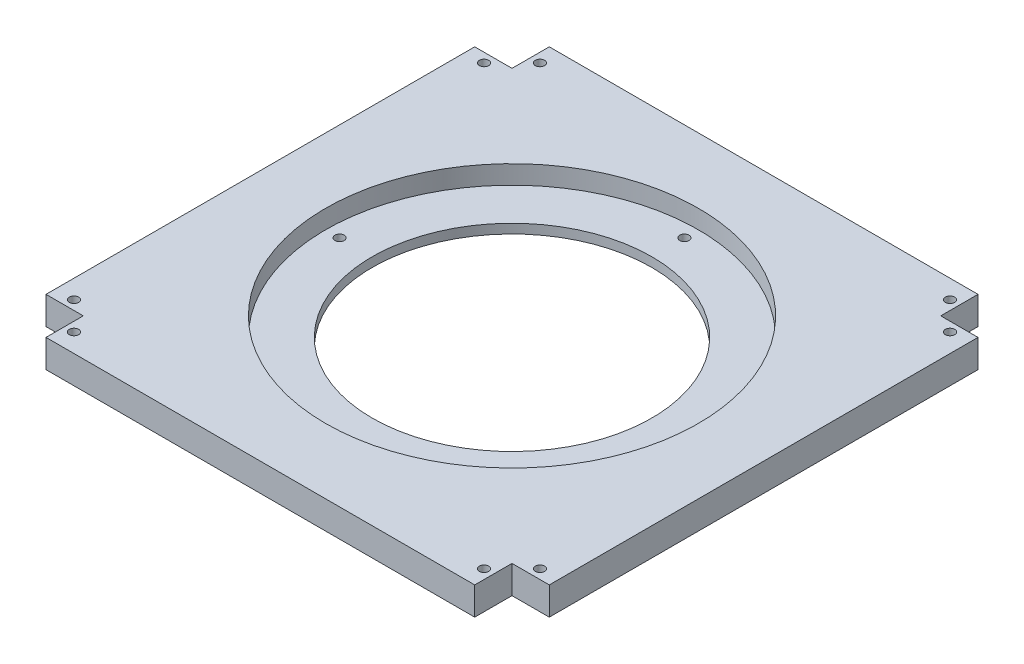
SolidWorks part; units mm, degrees
ref_plane "Front Plane" through (0, 0, 0) normal (0, 0, 1) x (1, 0, 0)
ref_plane "Top Plane" through (0, 0, 0) normal (0, 1, 0) x (1, 0, 0)
ref_plane "Right Plane" through (0, 0, 0) normal (1, 0, 0) x (0, 0, -1)
sketch "Sketch1" plane through (0, 0, 0) normal (0, 1, 0) x (1, 0, 0)
  line L21 (0, 0) -> (270, 0)
  line L22 (0, 0) -> (0, 270)
  line L23 (0, 270) -> (270, 270)
  line L24 (270, 0) -> (270, 270)
  line L44 (135, 270) -> (135, 0) construction
  line L45 (0, 135) -> (270, 135) construction
  dimension "D1" = 270
  dimension "D2" = 270
extrude "Boss-Extrude1" add sketch "Sketch1" along normal blind 15
sketch "Sketch8" plane through (0, 15, 0) normal (0, 1, 0) x (1, 0, 0)
  line L1 (0, 270) -> (20, 270)
  line L2 (0, 270) -> (0, 250)
  line L3 (0, 250) -> (20, 250)
  line L4 (20, 270) -> (20, 250)
  line L5 (270, 270) -> (250, 270)
  line L6 (270, 270) -> (270, 250)
  line L7 (270, 250) -> (250, 250)
  line L8 (250, 270) -> (250, 250)
  line L9 (270, 0) -> (250, 0)
  line L10 (270, 0) -> (270, 20)
  line L11 (270, 20) -> (250, 20)
  line L12 (250, 0) -> (250, 20)
  line L13 (0, 0) -> (20, 0)
  line L14 (0, 0) -> (0, 20)
  line L15 (0, 20) -> (20, 20)
  line L16 (20, 0) -> (20, 20)
  dimension "D1" = 20
  dimension "D2" = 20
  dimension "D3" = 20
  dimension "D4" = 20
  dimension "D5" = 20
  dimension "D6" = 20
  dimension "D7" = 20
  dimension "D8" = 20
extrude "Cut-Extrude1" cut sketch "Sketch8" against normal through all
sketch "Sketch9" plane through (0, 15, 0) normal (0, 1, 0) x (1, 0, 0)
  line L0 (135, 270) -> (135, 0) construction
  line L1 (250, 270) -> (20, 270) construction
  line L2 (20, 0) -> (250, 0) construction
  line L3 (0, 135) -> (270, 135) construction
  line L4 (0, 250) -> (0, 20) construction
  line L5 (270, 20) -> (270, 250) construction
  line L6 (260, 250) -> (260, 20) construction
  line L7 (250, 250) -> (270, 250) construction
  line L8 (270, 20) -> (250, 20) construction
  line L9 (250, 10) -> (20, 10) construction
  line L10 (250, 20) -> (250, 0) construction
  line L11 (20, 0) -> (20, 20) construction
  line L12 (10, 250) -> (10, 20) construction
  line L13 (0, 250) -> (20, 250) construction
  line L14 (20, 20) -> (0, 20) construction
  line L15 (20, 260) -> (250, 260) construction
  line L16 (20, 250) -> (20, 270) construction
  line L17 (250, 270) -> (250, 250) construction
  circle A0 centre (10, 245) radius 2.5
  circle A1 centre (10, 25) radius 2.5
  circle A2 centre (25, 10) radius 2.5
  circle A3 centre (245, 10) radius 2.5
  circle A4 centre (260, 25) radius 2.5
  circle A5 centre (260, 245) radius 2.5
  circle A6 centre (245, 260) radius 2.5
  circle A7 centre (25, 260) radius 2.5
  dimension "D1" = 5
  dimension "D2" = 5
  dimension "D3" = 5
  dimension "D4" = 5
  dimension "D5" = 5
  dimension "D6" = 5
  dimension "D7" = 5
  dimension "D8" = 5
  dimension "D9" = 5
  dimension "D10" = 5
  dimension "D11" = 5
  dimension "D12" = 5
  dimension "D13" = 5
  dimension "D14" = 5
  dimension "D15" = 5
  dimension "D16" = 5
extrude "Cut-Extrude2" cut sketch "Sketch9" against normal through all
sketch "Sketch10" plane through (0, 15, 0) normal (0, 1, 0) x (1, 0, 0)
  line L0 (135, 270) -> (135, 0) construction
  line L2 (250, 270) -> (20, 270) construction
  line L3 (20, 0) -> (250, 0) construction
  line L4 (0, 135) -> (270, 135) construction
  line L5 (0, 250) -> (0, 20) construction
  line L6 (270, 20) -> (270, 250) construction
  circle A0 centre (135, 135) radius 100
  dimension "D1" = 200
extrude "Cut-Extrude3" cut sketch "Sketch10" against normal blind 10
sketch "Sketch12" plane through (0, 5, 0) normal (0, 1, 0) x (1, 0, 0)
  line L0 (135, 235) -> (135, 35) construction
  line L1 (35, 135) -> (235, 135) construction
  circle A0 centre (135, 135) radius 100 construction
  circle A1 centre (135, 135) radius 100 construction
  circle A2 centre (135, 135) radius 75
  circle A3 centre (135, 227.5) radius 2.5
  circle A4 centre (227.5, 135) radius 2.5
  circle A5 centre (135, 42.5) radius 2.5
  circle A6 centre (42.5, 135) radius 2.5
  dimension "D1" = 150
  dimension "D2" = 5
  dimension "D3" = 5
  dimension "D4" = 5
  dimension "D5" = 5
  dimension "D6" = 92.5
  dimension "D7" = 92.5
  dimension "D8" = 92.5
  dimension "D9" = 92.5
extrude "Cut-Extrude4" cut sketch "Sketch12" against normal through all
